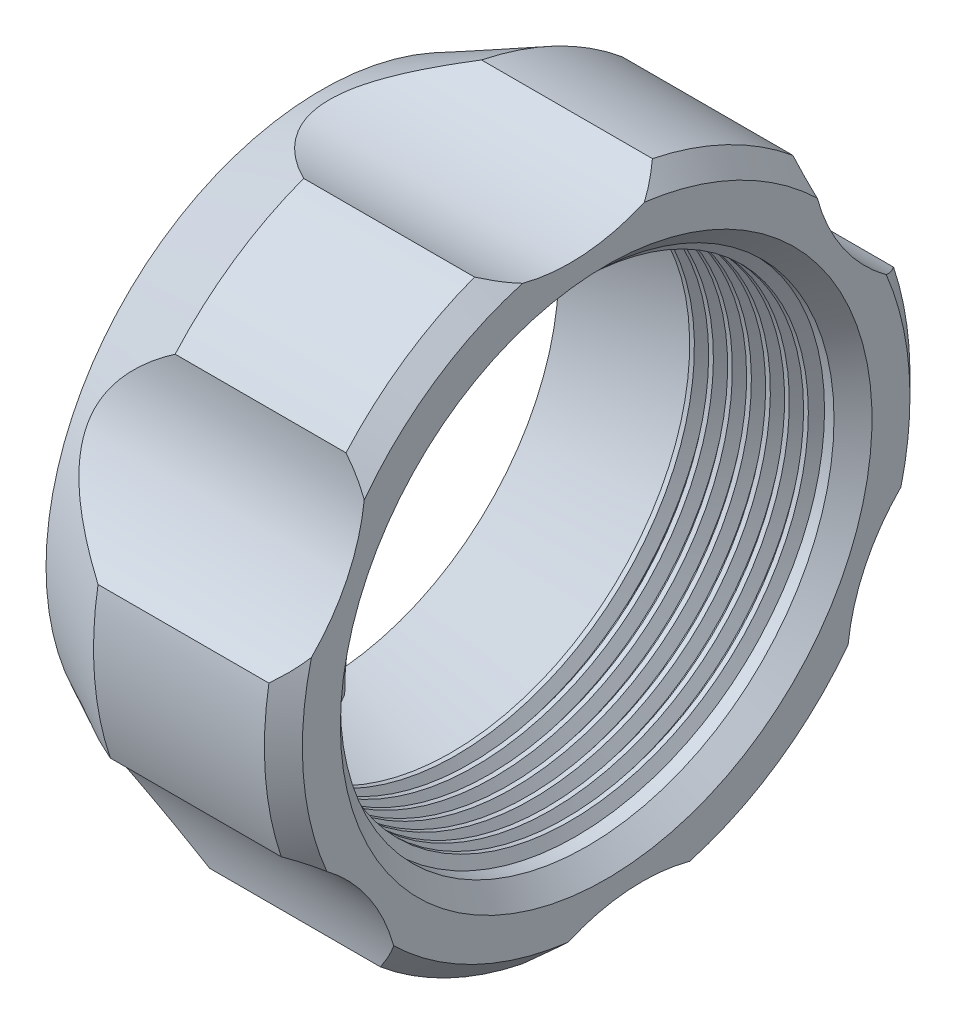
SolidWorks part; units mm, degrees
material "1060 Сплав"
ref_plane "Спереди" through (0, 0, 0) normal (0, 0, 1) x (1, 0, 0)
ref_plane "Сверху" through (0, 0, 0) normal (0, 1, 0) x (1, 0, 0)
ref_plane "Справа" through (0, 0, 0) normal (1, 0, 0) x (0, 0, -1)
sketch "Эскиз1" plane through (0, 0, 0) normal (0, 1, 0) x (1, 0, 0)
  line L0 (0, 2.0036) -> (79.9399, 2.0036) construction
  line L1 (30.6373, 19.0036) -> (20.6373, 19.0036)
  line L2 (20.6373, 19.0036) -> (15.6373, 16.5036)
  line L3 (15.6373, 16.5036) -> (15.6373, 14.5036)
  line L4 (15.6373, 14.5036) -> (21.6373, 17.0036)
  line L5 (21.6373, 17.0036) -> (23.6373, 15.0036)
  line L6 (30.6373, 15.0036) -> (30.6373, 19.0036)
  line L7 (30.6373, 15.0036) -> (23.6373, 15.0036)
  dimension "D1" = 10
  dimension "D2" = 15
  dimension "D3" = 13
  dimension "D4" = 12.5
  dimension "D5" = 15
  dimension "D6" = 7
  dimension "D7" = 2
  dimension "D8" = 17
  dimension "D9" = 9
revolve "Повернуть1" add sketch "Эскиз1" angle 360 about L0
chamfer "Фаска1" distance 1 angle 45 1 edges at (30.6373, 0, 14.9964)
chamfer "Фаска2" distance 1 angle 45 1 edges at (30.6373, 0, 10.9964)
thread "Резьба1" pitch 1 method extrude profile "Профиль резьбы1" start angle 0, offset 0, length 7, pitch 1, diameter 26
ref_plane "Плоскость1" through (29.6373, 0, 10.9964) normal (0, -1, 0) x (0, 0, 1)
sketch "Профиль резьбы1" plane through (29.6373, 0, 10.9964) normal (0, -1, 0) x (0, 0, 1)
  line L0 (0, 0) -> (0, 1) construction
  line L11 (0, 0) -> (0, 0.875)
  line L12 (0, 0.875) -> (-0.5413, 0.5625)
  line L13 (-0.5413, 0.5625) -> (-0.5413, 0.3125)
  line L15 (-0.5413, 0.3125) -> (0, 0)
  line L17 (-0.5413, 0.4375) -> (0, 0.4375) construction
  point P2 (0, 0)
  dimension "Pitch" = 1
  dimension "Profile_Angle" = 60
  dimension "Profile_Land" = 0.25
  dimension "Profile_Height" = 0.5413
sketch "Эскиз4" plane through (30.6373, 0, 0) normal (1, 0, 0) x (0, 0, -1)
  line L1 (24.3824, -10.7298) -> (22.4853, 14.0157) construction
  line L2 (22.4853, 14.0157) -> (0.1065, 24.7455) construction
  line L3 (0.1065, 24.7455) -> (-20.3753, 10.7298) construction
  line L4 (-20.3753, 10.7298) -> (-18.4782, -14.0157) construction
  line L5 (-18.4782, -14.0157) -> (3.9007, -24.7455) construction
  line L6 (3.9007, -24.7455) -> (24.3824, -10.7298) construction
  circle A0 centre (2.0036, 0) radius 21.4931 construction
  circle A1 centre (-20.3753, 10.7298) radius 9.6943
  circle A2 centre (-18.4782, -14.0157) radius 9.6435
  circle A3 centre (3.9007, -24.7455) radius 9.6943
  circle A4 centre (24.3824, -10.7298) radius 9.6943
  circle A5 centre (22.4853, 14.0157) radius 9.6943
  circle A6 centre (0.1065, 24.7455) radius 9.6943
extrude "Вырез-Вытянуть1" cut sketch "Эскиз4" against normal blind 15
